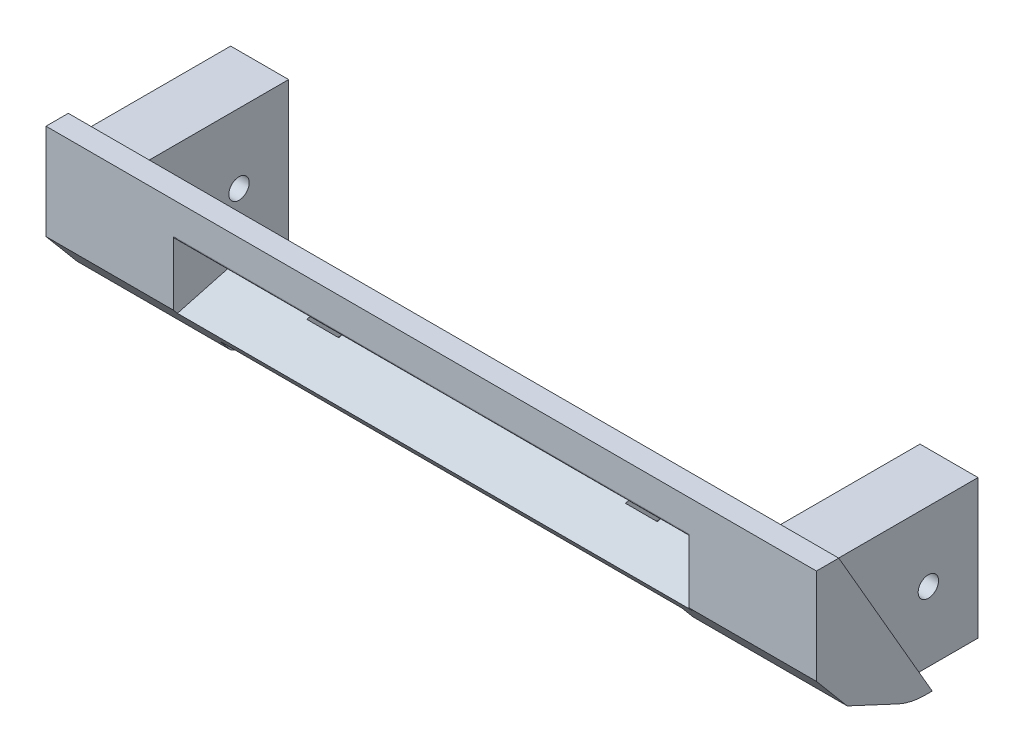
SolidWorks part; units mm, degrees
ref_plane "Front Plane" through (0, 0, 0) normal (0, 0, 1) x (1, 0, 0)
ref_plane "Top Plane" through (0, 0, 0) normal (0, 1, 0) x (1, 0, 0)
ref_plane "Right Plane" through (0, 0, 0) normal (1, 0, 0) x (0, 0, -1)
sketch "Sketch1" plane through (0, 0, 0) normal (1, 0, 0) x (0, 0, -1)
  line L0 (0, 0) -> (-29.3294, 50.8)
  line L1 (0, 0) -> (50, 0) construction
  line L2 (-29.3294, 50.8) -> (-36.3294, 50.8)
  line L3 (-36.3294, 13.8) -> (-6.7352, 0)
  line L6 (-36.3294, 50.8) -> (-36.3294, 13.8)
  line L7 (-6.7352, 0) -> (0, 0)
  line L8 (0, 0) -> (0, 21.8413) construction
  dimension "D1" = 65
  dimension "D2" = 6.7352
  dimension "D3" = 37
extrude "Boss-Extrude2" add sketch "Sketch1" along normal mid plane 241.8
sketch "Sketch2" plane through (0, 0, 0) normal (0, 0, 1) x (1, 0, 0)
  line L0 (0, 0) -> (0, 50.8) construction
  line L5 (117.675, 47.625) -> (98.675, 47.625) construction
  line L6 (117.675, 47.625) -> (117.675, 3.175) construction
  line L11 (117.675, 3.175) -> (98.675, 3.175) construction
  line L12 (98.675, 47.625) -> (98.675, 3.175) construction
  line L14 (117.275, 47.225) -> (117.275, 3.575)
  line L15 (117.275, 3.575) -> (99.075, 3.575)
  line L21 (119.775, 0) -> (-119.6, 0) construction
  line L28 (99.075, 47.225) -> (99.075, 3.575)
  line L29 (117.275, 47.225) -> (99.075, 47.225)
  line L30 (-98.675, 47.625) -> (-98.675, 3.175) construction
  line L31 (-117.675, 3.175) -> (-98.675, 3.175) construction
  line L32 (-117.675, 47.625) -> (-117.675, 3.175) construction
  line L33 (-117.675, 47.625) -> (-98.675, 47.625) construction
  line L34 (-117.275, 47.225) -> (-99.075, 47.225)
  line L35 (-99.075, 47.225) -> (-99.075, 3.575)
  line L36 (-117.275, 3.575) -> (-99.075, 3.575)
  line L37 (-117.275, 47.225) -> (-117.275, 3.575)
  line L40 (120.9, 50.8) -> (-120.9, 50.8) construction
  line L41 (120.9, 0) -> (120.9, 50.8) construction
  dimension "D2" = 19
  dimension "D4" = 3.175
  dimension "D7" = 3.225
  dimension "D1" = 197.35
  dimension "D3" = 3.175
  dimension "D5" = 0.4
extrude "Boss-Extrude1" add sketch "Sketch2" along normal up to surface and the other way blind 18 up to face at (0, 25.4, 14.6647)
sketch "Sketch12" plane through (0, -2.5797, 1.2029) normal (0, -0.9063, 0.4226) x (1, 0, 0)
  line L0 (-95.2, -603.0139) -> (-95.2, 0.9459) construction
  line L1 (-95.2, -603.0139) -> (-95.2, 0.9459) construction
  line L2 (120.9, 0) -> (-120.9, 0) construction
  line L3 (70, 15) -> (-70, 15)
  line L4 (70, 15) -> (70, 0)
  line L5 (70, 0) -> (-70, 0)
  line L6 (-70, 15) -> (-70, 0)
  line L7 (70, 15) -> (-70, 0) construction
  line L8 (70, 0) -> (-70, 15) construction
  line L10 (95.2, 44.3946) -> (-95.2, 44.3946)
  line L11 (95.2, 44.3946) -> (95.2, 19.3946)
  line L12 (95.2, 19.3946) -> (-95.2, 19.3946)
  line L13 (-95.2, 44.3946) -> (-95.2, 19.3946)
  line L14 (95.2, 44.3946) -> (-95.2, 19.3946) construction
  line L15 (95.2, 19.3946) -> (-95.2, 44.3946) construction
  line L16 (-120.6, 54.3946) -> (120.6, 54.3946) construction
  point P2 (0, 7.5)
  point P11 (0, 31.8946)
  dimension "D1" = 15
  dimension "D2" = 140
  dimension "D3" = 10
  dimension "D4" = 25
  dimension "D5" = 4.3946
extrude "Cut-Extrude4" [suppressed] cut sketch "Sketch12" against normal up to next
hole_wizard "M6 Clearance Hole1" positions "Sketch11" profile "Sketch10" hole size "M6" standard "ANSI Metric" end condition through all
sketch "Sketch11" plane through (117.275, 0, 0) normal (1, 0, 0) x (0, 0, -1)
  point P0 (2.4206, 25.4)
sketch "Sketch10" plane through (117.275, 25.4, -2.4206) normal (0, 1, 0) x (0, 0, -1)
  line L0 (0, 0) -> (0, 238.175)
  line L1 (0, 238.175) -> (3.2, 238.175)
  line L2 (3.2, 238.175) -> (3.2, 0)
  line L5 (3.2, 0) -> (0, 0)
  line L11 (0, -6.35) -> (0, 107.95) construction
  dimension "Thru Hole Dia." = 6.4
  dimension "Thru Hole Depth" = 238.175
sketch "Sketch13" plane through (0, 0, 0) normal (0, 0, 1) x (1, 0, 0)
  line L0 (120.9, 0) -> (-120.9, 0) construction
  line L1 (-72.5, 13.5) -> (72.5, 13.5)
  line L2 (-72.5, 13.5) -> (-72.5, 0)
  line L3 (-72.5, 0) -> (72.5, 0)
  line L4 (72.5, 13.5) -> (72.5, 0)
  line L5 (-72.5, 13.5) -> (72.5, 0) construction
  line L6 (-72.5, 0) -> (72.5, 13.5) construction
  line L7 (120.9, 50.8) -> (-120.9, 50.8) construction
  line L8 (-80.9, 23.8) -> (80.9, 23.8)
  line L9 (-80.9, 23.8) -> (-80.9, 37.8)
  line L10 (-80.9, 37.8) -> (80.9, 37.8)
  line L11 (80.9, 23.8) -> (80.9, 37.8)
  line L12 (-80.9, 23.8) -> (80.9, 37.8) construction
  line L13 (-80.9, 37.8) -> (80.9, 23.8) construction
  line L14 (-120.9, 50.8) -> (-120.9, 13.8) construction
  line L15 (0, 50.8) -> (0, -69.7748) construction
  point P0 (0, 6.75)
  point P7 (0, 30.8)
  dimension "D1" = 13.5
  dimension "D2" = 13
  dimension "D3" = 40
  dimension "D4" = 14
  dimension "D5" = 145
extrude "Cut-Extrude6" cut sketch "Sketch13" against normal through all both and the other way through all
chamfer "Chamfer5" distance 18 angle 15 1 edges at (0, 37.8, 21.8238) first distance on face at (0, 37.8, 29.0766)
chamfer "Chamfer6" distance 18 angle 15 1 edges at (0, 23.8, 36.3294) first distance on face at (0, 23.8, 25.0352)
chamfer "Chamfer7" distance 7 angle 40 1 edges at (0, 13.8, 36.3294) first distance on face at (0, 28.8566, 36.3294)
sketch "Sketch14" plane through (0, 13.5, 0) normal (0, -1, 0) x (1, 0, 0)
  line L0 (-50, 11.7942) -> (50, 11.7942) construction
  line L1 (72.5, 7.7942) -> (-72.5, 7.7942) construction
  line L2 (46.5, 15.7942) -> (53.5, 15.7942)
  line L3 (46.5, 15.7942) -> (46.5, 7.7942)
  line L4 (46.5, 7.7942) -> (53.5, 7.7942)
  line L5 (53.5, 15.7942) -> (53.5, 7.7942)
  line L6 (46.5, 15.7942) -> (53.5, 7.7942) construction
  line L7 (46.5, 7.7942) -> (53.5, 15.7942) construction
  line L9 (-53.5, 15.7942) -> (-46.5, 15.7942)
  line L10 (-53.5, 15.7942) -> (-53.5, 7.7942)
  line L11 (-53.5, 7.7942) -> (-46.5, 7.7942)
  line L12 (-46.5, 15.7942) -> (-46.5, 7.7942)
  line L13 (-53.5, 15.7942) -> (-46.5, 7.7942) construction
  line L14 (-53.5, 7.7942) -> (-46.5, 15.7942) construction
  point P0 (50, 11.7942)
  point P3 (0, 11.7942)
  dimension "D1" = 7
  dimension "D2" = 7
  dimension "D3" = 8
  dimension "D4" = 100
ref_plane "Plane2" through (0, 13.5, 7.7942) normal (0, 0.866, 0.5) x (-1, 0, 0)
sketch "Sketch15" plane through (0, 13.5, 7.7942) normal (0, 0.866, 0.5) x (-1, 0, 0)
  line L0 (-50, 3) -> (50, 3) construction
  line L1 (-72.5, 0) -> (72.5, 0) construction
  line L2 (-45, 6) -> (-55, 6)
  line L3 (-45, 6) -> (-45, 0)
  line L4 (-45, 0) -> (-55, 0)
  line L5 (-55, 6) -> (-55, 0)
  line L6 (-45, 6) -> (-55, 0) construction
  line L7 (-45, 0) -> (-55, 6) construction
  line L9 (45, 6) -> (55, 6)
  line L10 (45, 6) -> (45, 0)
  line L11 (45, 0) -> (55, 0)
  line L12 (55, 6) -> (55, 0)
  line L13 (45, 6) -> (55, 0) construction
  line L14 (45, 0) -> (55, 6) construction
  point P3 (0, 3)
  dimension "D1" = 10
  dimension "D2" = 10
  dimension "D3" = 6
  dimension "D4" = 100
extrude "Cut-Extrude8" cut sketch "Sketch15" along normal up to surface (14.7306 mm away) up to face at (0, 21.5558, 26.7049)
fillet "Fillet1" radius 4 1 edges at (0, 38.7363, 36.3294) second distance 1 first distance on face at (0, 40.3566, 30.2824)
fillet "Fillet2" radius 20 2 edges at (-96.7, 0, 6.7352) (96.7, 0, 6.7352)
equation "\"D1@Sketch2\"=\"RailSpacing\"+0.25in"
equation "\"RailSpacing\"= 191.mm"
equation "\"D1@Boss-Extrude2\"=\"RailSpacing\"+2in"
